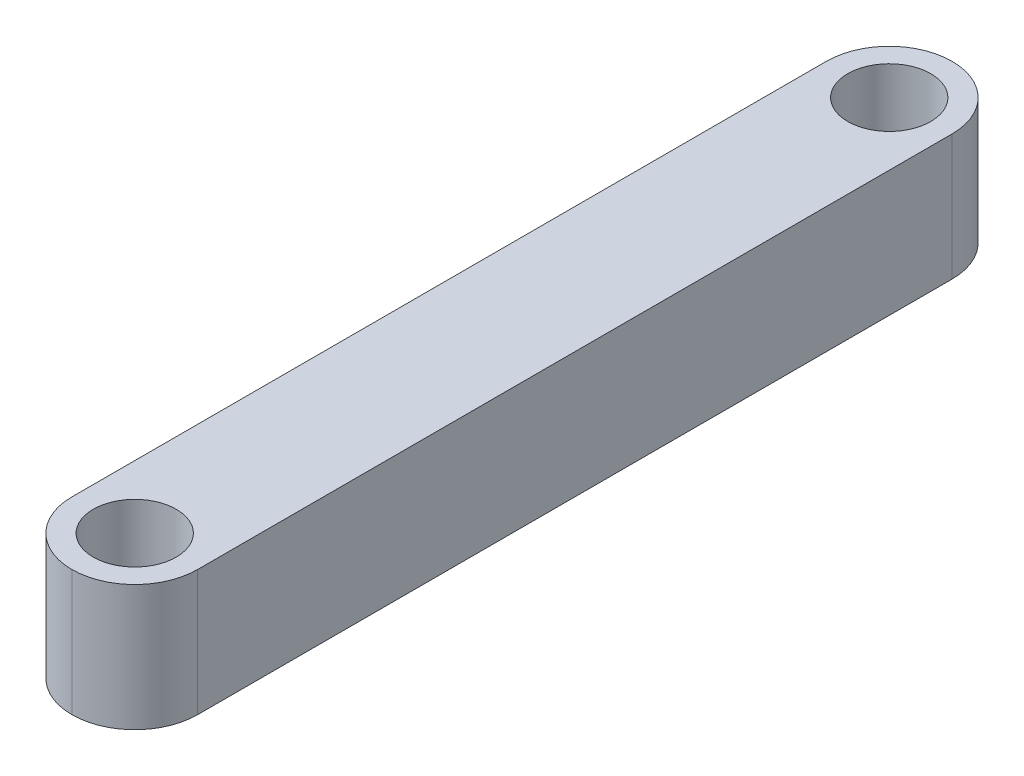
SolidWorks part; units mm, degrees
ref_plane "前视基准面" through (0, 0, 0) normal (0, 0, 1) x (1, 0, 0)
ref_plane "上视基准面" through (0, 0, 0) normal (0, 1, 0) x (1, 0, 0)
ref_plane "右视基准面" through (0, 0, 0) normal (1, 0, 0) x (0, 0, -1)
sketch "草图2" plane through (0, 0, 0) normal (0, 1, 0) x (1, 0, 0)
  line L1 (0, 0) -> (50, 0)
  line L2 (0, 0) -> (0, 350)
  line L3 (0, 350) -> (50, 350)
  line L4 (50, 0) -> (50, 350)
  circle A2 centre (25, 25) radius 16.5
  circle A3 centre (25, 325) radius 16.5
  dimension "D3" = 33
  dimension "D4" = 25
  dimension "D6" = 33
  dimension "D1" = 25
  dimension "D2" = 50
  dimension "D5" = 25
  dimension "D7" = 300
  dimension "D8" = 25
extrude "凸台-拉伸2" add sketch "草图2" along normal blind 50
fillet "圆角1" radius 25 2 edges at (50, 25, 0) (0, 25, 0)
fillet "圆角2" radius 25 2 edges at (50, 25, -350) (0, 25, -350)
